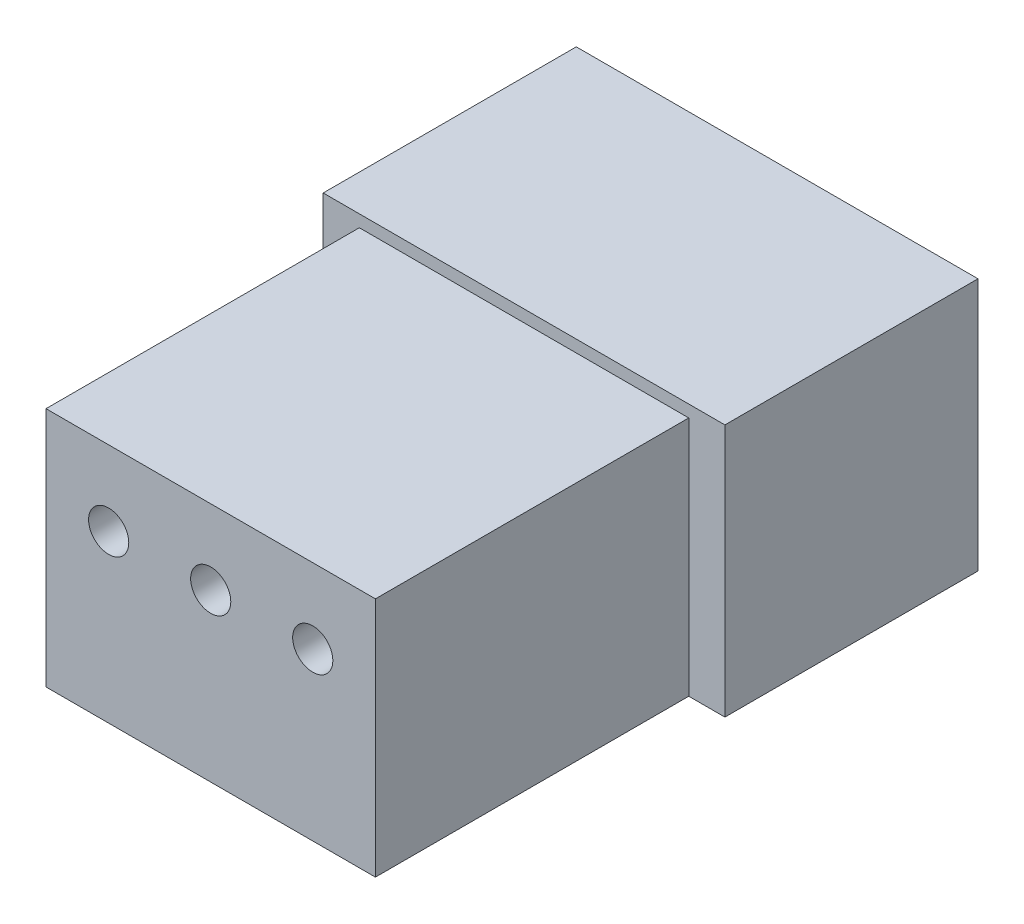
SolidWorks part; units mm, degrees
material "PEI"
ref_plane "前视基准面" through (0, 0, 0) normal (0, 0, 1) x (1, 0, 0)
ref_plane "上视基准面" through (0, 0, 0) normal (0, 1, 0) x (1, 0, 0)
ref_plane "右视基准面" through (0, 0, 0) normal (1, 0, 0) x (0, 0, -1)
other "Configuration Table"
sketch "草图1" plane through (0, 0, 0) normal (0, 0, 1) x (1, 0, 0)
  line L1 (0, 0) -> (10, 0)
  line L2 (0, 0) -> (0, 6.3)
  line L3 (0, 6.3) -> (10, 6.3)
  line L4 (10, 0) -> (10, 6.3)
  line L5 (0.7, 4.9) -> (9.3, 4.9)
  line L6 (0.7, 4.9) -> (0.7, 1)
  line L7 (0.7, 1) -> (9.3, 1)
  line L8 (9.3, 4.9) -> (9.3, 1)
  dimension "D1" = 10
  dimension "D2" = 6.3
  dimension "D3" = 1.4
  dimension "D4" = 0.7
  dimension "D5" = 0.7
  dimension "D6" = 1
extrude "凸台-拉伸1" add sketch "草图1" along normal blind 6.3
sketch "草图2" plane through (0, 0, 6.3) normal (0, 0, 1) x (1, 0, 0)
  line L1 (0.9, 6) -> (9.1, 6)
  line L2 (0.9, 6) -> (0.9, 0)
  line L3 (0.9, 0) -> (9.1, 0)
  line L4 (9.1, 6) -> (9.1, 0)
  line L6 (0, 6.3) -> (0, 0) construction
  line L7 (10, 0) -> (10, 6.3) construction
  point P4 (0, 0)
  point P5 (0, 0)
  point P8 (0, 0)
  point P9 (0, 0)
  dimension "D1" = 6
  dimension "D2" = 0.9
  dimension "D3" = 0.9
extrude "凸台-拉伸2" add sketch "草图2" along normal blind 7.8
sketch "草图3" plane through (0, 0, 6.3) normal (0, 0, -1) x (-1, 0, 0)
  line L4 (0, 0) -> (0, 6.3)
  line L5 (0, 6.3) -> (-10, 6.3)
  line L6 (-10, 6.3) -> (-10, 0)
  line L7 (-10, 0) -> (0, 0)
  line L8 (0, 0) -> (0, 6.3)
  line L9 (0, 6.3) -> (-10, 6.3)
  line L10 (-10, 6.3) -> (-10, 0)
  line L11 (-10, 0) -> (0, 0)
  dimension "D1" = 0
extrude "凸台-拉伸3" add sketch "草图3" along normal blind 1
sketch "草图4" plane through (0, 0, 14.1) normal (0, 0, 1) x (1, 0, 0)
  line L0 (5, 6) -> (5, 0) construction
  line L1 (9.1, 6) -> (0.9, 6) construction
  line L2 (0.9, 0) -> (9.1, 0) construction
  circle A0 centre (2.46, 4.1382) radius 0.5
  circle A1 centre (5, 4.1382) radius 0.5
  circle A2 centre (7.54, 4.1382) radius 0.5
  point P12 (0, 0)
  point P13 (0, 0)
  dimension "D2" = 1
  dimension "D1" = 2.54
extrude "切除-拉伸1" cut sketch "草图4" against normal through all both and the other way through all
other "连接点1" parameters "直径"=4, "端头长度"=6
ref_axis "基准轴1" through (2.46, 4.1382, 15.3) along (0, 0, -1)
other "连接点2" parameters "直径"=4, "端头长度"=6
ref_axis "基准轴2" through (5, 4.1382, 15.3) along (0, 0, -1)
other "连接点3" parameters "直径"=4, "端头长度"=6
ref_axis "基准轴3" through (7.54, 4.1382, 15.3) along (0, 0, -1)
